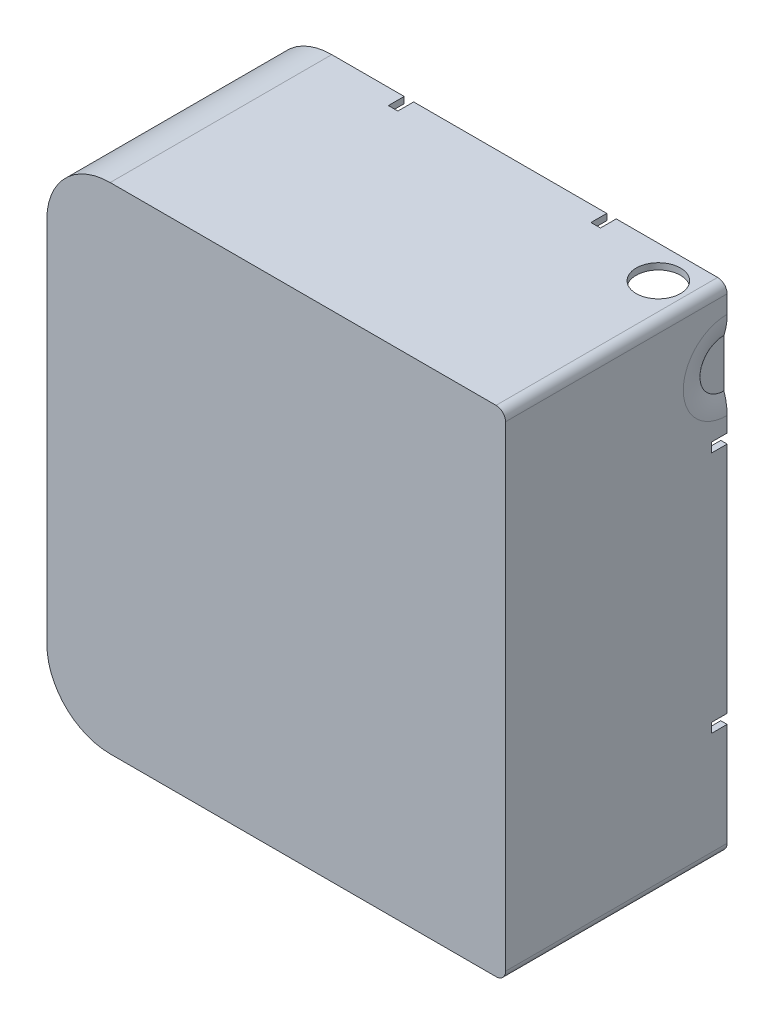
SolidWorks part; units mm, degrees
ref_plane "Plan de face" through (0, 0, 0) normal (0, 0, 1) x (1, 0, 0)
ref_plane "Plan de dessus" through (0, 0, 0) normal (0, 1, 0) x (1, 0, 0)
ref_plane "Plan de droite" through (0, 0, 0) normal (1, 0, 0) x (0, 0, -1)
sketch "Esquisse2" plane through (0, 0, 0) normal (0, 0, 1) x (1, 0, 0)
  line L10 (-132.8307, 151.04) -> (12.0772, 151.04)
  line L11 (-132.8307, -5.2905) -> (12.0772, -5.2905)
  line L12 (-132.8307, -5.2905) -> (-132.8307, 151.04)
  line L14 (12.0772, -5.2905) -> (12.0772, 151.04)
extrude "Boss.-Extru.1" add sketch "Esquisse2" along normal blind 70
shell "Coque1" thickness 2 removed face at (-60.3767, 72.8748, 0)
sketch "Troue matien spirobs" plane through (0, 0, 0) normal (0, 1, 0) x (1, 0, 0)
  line L0 (-133.3511, -54.9894) -> (-133.3511, -44.2159)
  line L1 (-133.3511, -44.2159) -> (-138.3511, -47.1026)
  line L2 (-133.3511, -54.9894) -> (-138.3511, -52.1026)
  line L3 (-138.3511, -52.1026) -> (-138.3511, -47.1026)
  line L8 (-121.1646, 959.3709) -> (-121.1646, 970.1444)
  line L9 (-121.1646, 970.1444) -> (-126.1646, 967.2577)
  line L10 (-121.1646, 959.3709) -> (-126.1646, 962.2577)
  line L11 (-126.1646, 962.2577) -> (-126.1646, 967.2577)
  line L12 (-120.1646, 957.6389) -> (-120.1646, 971.8765)
  line L13 (-120.1646, 971.8765) -> (-127.1646, 967.835)
  line L14 (-127.1646, 961.6803) -> (-127.1646, 967.835)
  line L15 (-120.1646, 957.6389) -> (-127.1646, 961.6803)
  line L16 (-121.1646, 959.3709) -> (-121.1646, 970.1444)
  line L17 (-121.1646, 970.1444) -> (-126.1646, 967.2577)
  line L18 (-121.1646, 959.3709) -> (-126.1646, 962.2577)
  line L19 (-126.1646, 962.2577) -> (-126.1646, 967.2577)
  line L20 (-120.1646, 957.6389) -> (-120.1646, 971.8765)
  line L21 (-120.1646, 971.8765) -> (-127.1646, 967.835)
  line L22 (-127.1646, 961.6803) -> (-127.1646, 967.835)
  line L23 (-120.1646, 957.6389) -> (-127.1646, 961.6803)
  line L28 (-132.8511, -55.8554) -> (-132.8511, -43.3499)
  line L29 (-132.8511, -43.3499) -> (-138.8511, -46.814)
  line L30 (-138.8511, -52.3913) -> (-138.8511, -46.814)
  line L31 (-132.8511, -55.8554) -> (-138.8511, -52.3913)
  dimension "D1" = 0.5
sketch "Esquisse6" plane through (0, 0, 0) normal (0, 1, 0) x (1, 0, 0)
  line L0 (-141.3702, -89.6078) -> (-141.3702, -78.8343)
  line L1 (-141.3702, -78.8343) -> (-146.3702, -81.7211)
  line L2 (-141.3702, -89.6078) -> (-146.3702, -86.7211)
  line L3 (-146.3702, -86.7211) -> (-146.3702, -81.7211)
  line L4 (-140.3702, -91.3399) -> (-140.3702, -77.1023)
  line L5 (-140.3702, -77.1023) -> (-147.3702, -81.1437)
  line L6 (-147.3702, -87.2984) -> (-147.3702, -81.1437)
  line L7 (-140.3702, -91.3399) -> (-147.3702, -87.2984)
sketch "Esquisse14" plane through (-132.8307, 0, 0) normal (-1, 0, 0) x (0, 0, 1)
  line L1 (63.7081, 121.0194) -> (34.9744, 121.0194)
  line L2 (63.7081, 121.0194) -> (63.7081, 19.443)
  line L3 (63.7081, 19.443) -> (34.9744, 19.443)
  line L4 (34.9744, 121.0194) -> (34.9744, 19.443)
extrude "Boss.-Extru.7" add sketch "Esquisse14" along normal blind 5.5 draft 10
extrude "Enlèv. mat.-Extru.5" cut sketch "Troue matien spirobs" along normal blind 137.5 contours L3 L2 L0 L1 | L31 L28 L29 L30 L2 L3 L1 L0 region at (-135.5461, 0, 49.6026) region at (-135.7817, 0, 54.0032)
sketch "Esquisse16" plane through (-132.8511, 0, 0) normal (-1, 0, 0) x (0, 0, 1)
  line L0 (49.6026, 121.0158) -> (49.6026, 19.4466)
  line L1 (55.8554, 121.0158) -> (43.3499, 121.0158) construction
  line L2 (43.3499, 19.4466) -> (55.8554, 19.4466) construction
  circle A0 centre (49.6026, 94.9889) radius 2
  circle A1 centre (49.6026, 50.4889) radius 2
  circle A2 centre (49.6026, 72.7389) radius 3
  dimension "D1" = 44.5
  dimension "D2" = 22.25
extrude "Enlèv. mat.-Extru.6" cut sketch "Esquisse16" against normal blind 3 contours L0 A0 | L0 A0 | L0 A1 | L0 A1 | A2 region at (-132.8511, 94.9889, 50.4515) region at (-132.8511, 50.4889, 50.4515) region at (-132.8511, 50.4889, 48.7538) region at (-132.8511, 94.9889, 48.7538)
sketch "Esquisse17" plane through (0, 149.04, 0) normal (0, -1, 0) x (1, 0, 0)
  line L1 (-63.6451, 15.451) -> (-71.6451, 15.451)
  line L2 (-63.6451, 15.451) -> (-63.6451, 39.451)
  line L3 (-63.6451, 39.451) -> (-71.6451, 39.451)
  line L4 (-71.6451, 15.451) -> (-71.6451, 39.451)
  line L25 (-121.9422, 39.1609) -> (-113.9422, 39.1609)
  line L26 (-121.9422, 39.1609) -> (-121.9422, 15.1609)
  line L27 (-121.9422, 15.1609) -> (-113.9422, 15.1609)
  line L28 (-113.9422, 39.1609) -> (-113.9422, 15.1609)
extrude "Boss.-Extru.8" add sketch "Esquisse17" along normal blind 33
sketch "Esquisse18" plane through (-63.6451, 0, 0) normal (1, 0, 0) x (0, 0, -1)
  line L1 (-22.2169, 133.2966) -> (-34.2579, 133.2966)
  line L2 (-22.2169, 133.2966) -> (-22.2169, 141.5112)
  line L3 (-22.2169, 141.5112) -> (-34.2579, 141.5112)
  line L4 (-34.2579, 133.2966) -> (-34.2579, 141.5112)
extrude "Enlèv. mat.-Extru.7" cut sketch "Esquisse18" against normal blind 9
sketch "Esquisse19" plane through (0, 116.04, 0) normal (0, -1, 0) x (1, 0, 0)
  circle A0 centre (-68.1102, 23.053) radius 0.8
  circle A1 centre (-68.1102, 32.8176) radius 0.8
  circle A2 centre (-117.543, 32.9387) radius 0.8
  circle A3 centre (-117.543, 22.9387) radius 0.8
extrude "Enlèv. mat.-Extru.8" cut sketch "Esquisse19" against normal blind 5
sketch "Esquisse20" plane through (0, -3.2905, 0) normal (0, 1, 0) x (1, 0, 0)
  line L0 (-113.5886, -39.3741) -> (-122.0886, -39.3741)
  line L1 (-63.0147, -40.3939) -> (-71.5147, -40.3939)
  line L2 (-63.0147, -40.3939) -> (-63.0147, -16.3939)
  line L3 (-63.0147, -16.3939) -> (-71.5147, -16.3939)
  line L4 (-71.5147, -40.3939) -> (-71.5147, -16.3939)
  line L5 (-113.5886, -39.3741) -> (-113.5886, -15.3741)
  line L6 (-113.5886, -15.3741) -> (-122.0886, -15.3741)
  line L7 (-122.0886, -39.3741) -> (-122.0886, -15.3741)
extrude "Boss.-Extru.9" add sketch "Esquisse20" along normal blind 33
sketch "Esquisse21" plane through (0, 29.7095, 0) normal (0, 1, 0) x (1, 0, 0)
  circle A0 centre (-68.0619, -22.5356) radius 0.8
  circle A1 centre (-68.0619, -32.603) radius 0.8
  circle A2 centre (-117.5778, -22.5356) radius 0.8
  circle A3 centre (-117.5619, -32.3722) radius 0.8
sketch "Esquisse22" plane through (-63.0147, 0, 0) normal (1, 0, 0) x (0, 0, -1)
  line L1 (-33.8377, 11.3027) -> (-21.9435, 11.3027)
  line L2 (-33.8377, 11.3027) -> (-33.8377, 4.5585)
  line L3 (-33.8377, 4.5585) -> (-21.9435, 4.5585)
  line L4 (-21.9435, 11.3027) -> (-21.9435, 4.5585)
extrude "Enlèv. mat.-Extru.9" cut sketch "Esquisse22" against normal blind 10
sketch "Esquisse23" plane through (0, 0, 70) normal (0, 0, 1) x (1, 0, 0)
  line L1 (-151.2198, -19.723) -> (26.4103, -19.723)
  line L2 (-151.2198, -19.723) -> (-151.2198, 168.463)
  line L3 (-151.2198, 168.463) -> (26.4103, 168.463)
  line L4 (26.4103, -19.723) -> (26.4103, 168.463)
sketch "Esquisse25" plane through (0, 0, 39.451) normal (0, 0, 1) x (1, 0, 0)
  line L0 (-71.6451, 116.04) -> (-71.6451, 149.04) construction
  line L1 (-71.6451, 116.04) -> (-63.6451, 116.04)
  line L2 (-71.6451, 116.04) -> (-71.6451, 129.5061)
  line L3 (-71.6451, 129.5061) -> (-63.6451, 129.5061)
  line L4 (-63.6451, 116.04) -> (-63.6451, 129.5061)
  line L5 (-63.6451, 116.04) -> (-63.6451, 149.04) construction
sketch "Esquisse26" plane through (0, 0, 39.1609) normal (0, 0, 1) x (1, 0, 0)
  line L0 (-121.9422, 116.04) -> (-121.9422, 149.04) construction
  line L1 (-121.9422, 116.04) -> (-113.9422, 116.04)
  line L2 (-121.9422, 116.04) -> (-121.9422, 129.3352)
  line L3 (-121.9422, 129.3352) -> (-113.9422, 129.3352)
  line L4 (-113.9422, 116.04) -> (-113.9422, 129.3352)
  line L5 (-113.9422, 116.04) -> (-113.9422, 149.04) construction
sketch "Esquisse27" plane through (0, 0, 39.3741) normal (0, 0, 1) x (1, 0, 0)
  line L0 (-122.0886, 29.7095) -> (-113.5886, 29.7095) construction
  line L1 (-122.0886, 29.7095) -> (-113.5886, 29.7095)
  line L2 (-122.0886, 29.7095) -> (-122.0886, 16.0179)
  line L3 (-122.0886, 16.0179) -> (-113.5886, 16.0179)
  line L4 (-113.5886, 29.7095) -> (-113.5886, 16.0179)
  line L5 (-122.0886, 29.7095) -> (-122.0886, -3.2905) construction
  line L6 (-113.5886, 29.7095) -> (-113.5886, -3.2905) construction
sketch "Esquisse28" plane through (0, 0, 40.3939) normal (0, 0, 1) x (1, 0, 0)
  line L0 (-63.0147, 29.7095) -> (-63.0147, -3.2905) construction
  line L1 (-63.0147, 29.7095) -> (-71.5147, 29.7095)
  line L2 (-63.0147, 29.7095) -> (-63.0147, 15.3299)
  line L3 (-63.0147, 15.3299) -> (-71.5147, 15.3299)
  line L4 (-71.5147, 29.7095) -> (-71.5147, 15.3299)
  line L5 (-71.5147, 29.7095) -> (-71.5147, -3.2905) construction
extrude "Boss.-Extru.10" add sketch "Esquisse25" along normal up to vertex (30.549 mm away) up to point (26.4103, 168.463, 70)
extrude "Boss.-Extru.11" add sketch "Esquisse26" along normal blind 30
extrude "Boss.-Extru.12" add sketch "Esquisse27" along normal blind 30
extrude "Boss.-Extru.14" add sketch "Esquisse28" along normal blind 29
sketch "Esquisse29" plane through (0, 151.04, 0) normal (0, 1, 0) x (1, 0, 0)
  circle A0 centre (0.6377, -10.2907) radius 7
extrude "Enlèv. mat.-Extru.11" cut sketch "Esquisse29" against normal blind 5
sketch "Esquisse30" plane through (0, -5.2905, 0) normal (0, -1, 0) x (1, 0, 0)
  line L1 (-53.2213, 20.1892) -> (-0.5031, 20.1892)
  line L2 (-53.2213, 20.1892) -> (-53.2213, 6.3712)
  line L3 (-53.2213, 6.3712) -> (-0.5031, 6.3712)
  line L4 (-0.5031, 20.1892) -> (-0.5031, 6.3712)
extrude "Enlèv. mat.-Extru.12" cut sketch "Esquisse30" against normal blind 5
fillet "Congé4" radius 20 4 edges at (-130.8307, -3.2905, 34) (-130.8307, 149.04, 34) (-132.8307, -5.2905, 35) (-132.8307, 151.04, 35)
fillet "Congé5" radius 3 2 edges at (12.0772, 151.04, 35) (12.0772, -5.2905, 35)
sketch "Esquisse31" plane through (12.0772, 0, 0) normal (1, 0, 0) x (0, 0, -1)
  line L0 (0, -2.2905) -> (0, 148.04) construction
  line L1 (0, 120.9914) -> (0, 136.1912)
  arc A0 (0, 136.1912) -> (0, 120.9914) centre (0, 128.5913) ccw
extrude "Enlèv. mat.-Extru.13" cut sketch "Esquisse31" against normal blind 1
fillet "Congé6" radius 20 1 edges at (12.0772, 128.5913, 7.5999)
extrude "Enlèv. mat.-Extru.14" cut sketch "Esquisse21" against normal blind 7
ref_plane "Plan1" through (12.0772, 114.7464, 0) normal (0, -1, 0) x (-1, 0, 0)
sketch "Esquisse34" plane through (0, 0, 0) normal (0, 0, -1) x (-1, 0, 0)
  line L0 (132.8307, 30.2528) -> (130.8307, 30.2528)
  line L1 (132.8307, 30.2528) -> (132.8307, 33.2528)
  line L2 (132.8307, 33.2528) -> (130.8307, 33.2528)
  line L3 (130.8307, 30.2528) -> (130.8307, 33.2528)
  line L4 (130.8307, 109.9504) -> (132.8307, 109.9504)
  line L5 (130.8307, 109.9504) -> (130.8307, 106.9504)
  line L6 (130.8307, 106.9504) -> (132.8307, 106.9504)
  line L7 (132.8307, 109.9504) -> (132.8307, 106.9504)
  line L8 (-10.0772, 30.2528) -> (-12.0772, 30.2528)
  line L9 (-10.0772, 30.2528) -> (-10.0772, 33.2528)
  line L10 (-10.0772, 33.2528) -> (-12.0772, 33.2528)
  line L11 (-12.0772, 30.2528) -> (-12.0772, 33.2528)
  line L12 (-10.0772, 109.9504) -> (-12.0772, 109.9504)
  line L13 (-10.0772, 109.9504) -> (-10.0772, 106.9504)
  line L14 (-10.0772, 106.9504) -> (-12.0772, 106.9504)
  line L15 (-12.0772, 109.9504) -> (-12.0772, 106.9504)
  line L16 (89.9492, 151.04) -> (86.9492, 151.04)
  line L17 (89.9492, 151.04) -> (89.9492, 149.04)
  line L18 (89.9492, 149.04) -> (86.9492, 149.04)
  line L19 (86.9492, 151.04) -> (86.9492, 149.04)
  line L20 (25.9487, 151.04) -> (22.9487, 151.04)
  line L21 (25.9487, 151.04) -> (25.9487, 149.04)
  line L22 (25.9487, 149.04) -> (22.9487, 149.04)
  line L23 (22.9487, 151.04) -> (22.9487, 149.04)
  line L24 (25.9487, -3.2905) -> (22.9487, -3.2905)
  line L25 (25.9487, -3.2905) -> (25.9487, -5.2905)
  line L26 (25.9487, -5.2905) -> (22.9487, -5.2905)
  line L27 (22.9487, -3.2905) -> (22.9487, -5.2905)
  line L28 (89.9492, -3.2905) -> (86.9492, -3.2905)
  line L29 (89.9492, -3.2905) -> (89.9492, -5.2905)
  line L30 (89.9492, -5.2905) -> (86.9492, -5.2905)
  line L31 (86.9492, -3.2905) -> (86.9492, -5.2905)
  line L32 (112.8307, -5.2905) -> (-9.0772, -5.2905) construction
  line L33 (110.8307, -3.2905) -> (-10.0772, -3.2905) construction
  line L34 (130.8307, 129.04) -> (130.8307, 16.7095) construction
  line L35 (132.8307, 131.04) -> (132.8307, 14.7095) construction
  line L36 (-10.0772, 149.04) -> (110.8307, 149.04) construction
  line L37 (-9.0772, 151.04) -> (112.8307, 151.04) construction
  line L38 (-12.0772, -2.2905) -> (-12.0772, 114.7464) construction
  line L39 (-10.0772, -3.2905) -> (-10.0772, 149.04) construction
  point P32 (0, 0)
  point P33 (86.9492, -5.2905)
  point P36 (0, 0)
  point P37 (89.9492, -3.2905)
  point P40 (0, 0)
  point P41 (22.9487, -5.2905)
  point P42 (0, 0)
  point P43 (26.4295, -3.821)
  point P44 (25.9487, -3.2905)
  point P45 (0, 0)
  point P46 (130.8307, 30.2528)
  point P49 (132.8307, 33.2528)
  point P52 (0, 0)
  point P53 (132.8307, 106.9504)
  point P54 (0, 0)
  point P55 (0, 0)
  point P56 (130.8307, 109.9504)
  point P57 (0, 0)
  point P58 (89.9492, 149.04)
  point P61 (0, 0)
  point P62 (86.9492, 151.04)
  point P65 (25.9487, 151.04)
  point P66 (0, 0)
  point P67 (25.9487, 149.04)
  point P68 (0, 0)
  point P69 (-12.0772, 106.9504)
  point P72 (0, 0)
  point P73 (-10.0772, 109.9504)
  point P76 (0, 0)
  point P77 (-12.0772, 33.2528)
  point P78 (0, 0)
  point P79 (-10.0772, 30.2528)
extrude "Enlèv. mat.-Extru.15" cut sketch "Esquisse34" against normal blind 5
